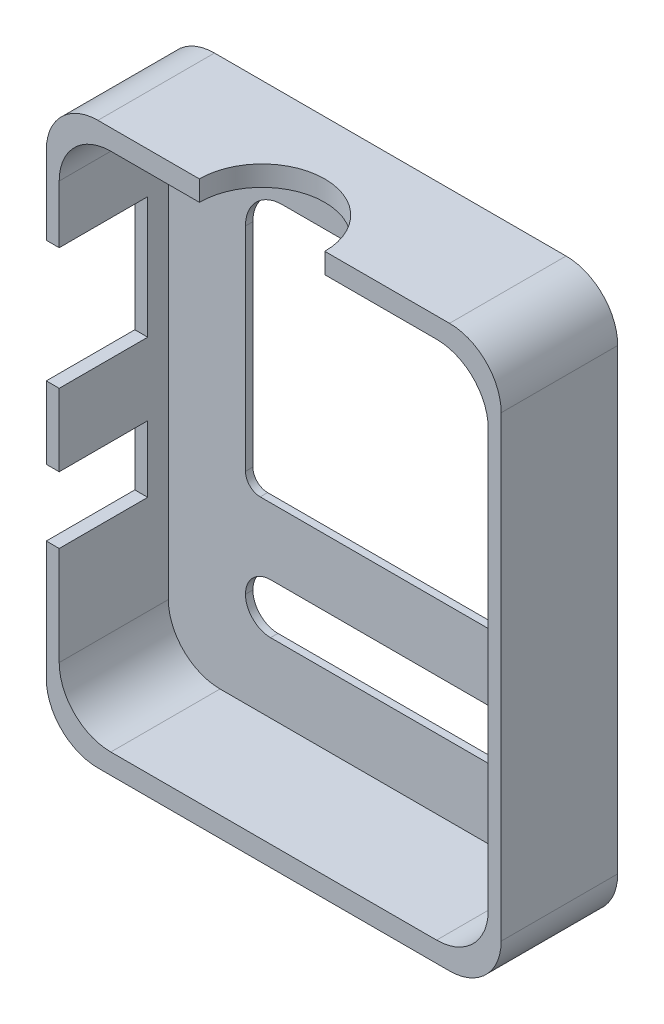
SolidWorks part; units mm, degrees
ref_plane "Front Plane" through (0, 0, 0) normal (0, 0, 1) x (1, 0, 0)
ref_plane "Top Plane" through (0, 0, 0) normal (0, 1, 0) x (1, 0, 0)
ref_plane "Right Plane" through (0, 0, 0) normal (1, 0, 0) x (0, 0, -1)
sketch "Sketch1" plane through (0, 0, 0) normal (0, 0, 1) x (1, 0, 0)
  line L1 (0, 0) -> (61.658, 0)
  line L2 (0, 0) -> (0, 76.028)
  line L3 (0, 76.028) -> (61.658, 76.028)
  line L4 (61.658, 0) -> (61.658, 76.028)
  dimension "D1" = 61.658
  dimension "D2" = 76.2688
extrude "Boss-Extrude1" add sketch "Sketch1" along normal blind 15.8
sketch "Sketch3" plane through (0, 0, 15.8) normal (0, 0, 1) x (1, 0, 0)
  line L0 (0, 76.028) -> (0, 0) construction
  line L1 (1.75, 2.75) -> (59.908, 2.75)
  line L2 (1.75, 2.75) -> (1.75, 73.278)
  line L3 (1.75, 73.278) -> (59.908, 73.278)
  line L4 (59.908, 2.75) -> (59.908, 73.278)
  line L5 (61.658, 76.028) -> (0, 76.028) construction
  dimension "D1" = 70.528
  dimension "D2" = 58.158
  dimension "D3" = 1.75
  dimension "D4" = 2.75
extrude "Cut-Extrude2" cut sketch "Sketch3" against normal blind 14.8
fillet "Fillet1" radius 7 1 edges at (61.658, 76.028, 7.9)
fillet "Fillet2" radius 7 3 edges at (0, 0, 7.9) (61.658, 0, 7.9) (1.75, 73.278, 8.4)
fillet "Fillet3" radius 7 4 edges at (1.75, 2.75, 8.4) (59.908, 73.278, 8.4) (59.908, 2.75, 8.4) (0, 76.028, 7.9)
sketch "Sketch4" plane through (0, 0, 15.8) normal (0, 0, 1) x (1, 0, 0)
  line L0 (0, 69.028) -> (0, 7) construction
  line L1 (0, 58.4447) -> (1.75, 58.4447)
  line L2 (0, 58.4447) -> (0, 41.9447)
  line L3 (0, 41.9447) -> (1.75, 41.9447)
  line L4 (1.75, 58.4447) -> (1.75, 41.9447)
  line L5 (1.75, 66.278) -> (1.75, 9.75) construction
  dimension "D1" = 1.75
  dimension "D2" = 16.5
extrude "Cut-Extrude3_switch" cut sketch "Sketch4" against normal blind 12
sketch "Sketch5" plane through (0, 0, 15.8) normal (0, 0, 1) x (1, 0, 0)
  line L0 (0, 41.9447) -> (0, 7) construction
  line L1 (0, 32.144) -> (1.75, 32.144)
  line L2 (0, 32.144) -> (0, 23.144)
  line L3 (0, 23.144) -> (1.75, 23.144)
  line L4 (1.75, 32.144) -> (1.75, 23.144)
  line L5 (1.75, 66.278) -> (1.75, 9.75) construction
  dimension "D1" = 9
extrude "Cut-Extrude4_usb" cut sketch "Sketch5" against normal blind 12
sketch "Sketch6" plane through (0, 76.028, 0) normal (0, 1, 0) x (1, 0, 0)
  line L0 (54.658, -15.8) -> (7, -15.8) construction
  line L2 (7, 0) -> (7, -15.8) construction
  circle A0 centre (29.25, -15.8) radius 8.5
  point P6 (0, 0)
  point P7 (0, 0)
  dimension "D1" = 22.25
extrude "Cut-Extrude4_sonic" cut sketch "Sketch6" against normal blind 2.75
sketch "Sketch7" plane through (0, 0, 0) normal (0, 0, -1) x (-1, 0, 0)
  line L0 (-61.658, 7) -> (-61.658, 69.028) construction
  line L1 (-49.458, 63.828) -> (-12.2, 63.828)
  line L2 (-49.458, 63.828) -> (-49.458, 28.028)
  line L3 (-49.458, 28.028) -> (-12.2, 28.028)
  line L4 (-12.2, 63.828) -> (-12.2, 28.028)
  line L6 (0, 69.028) -> (0, 7) construction
  line L7 (-54.658, 76.028) -> (-7, 76.028) construction
  point P8 (-30.829, 63.828)
  dimension "D1" = 12.2
  dimension "D2" = 12.2
  dimension "D3" = 12.2
  dimension "D4" = 48
extrude "Cut-Extrude5_LcdMain" cut sketch "Sketch7" against normal blind 1
sketch "Sketch8" plane through (0, 0, 0) normal (0, 0, -1) x (-1, 0, 0)
  line L0 (-61.658, 7) -> (-61.658, 69.028) construction
  line L1 (-49.458, 12.2) -> (-12.2, 12.2)
  line L2 (-49.458, 12.2) -> (-49.458, 19)
  line L3 (-49.458, 19) -> (-12.2, 19)
  line L4 (-12.2, 12.2) -> (-12.2, 19)
  line L5 (0, 69.028) -> (0, 7) construction
  line L6 (-7, 0) -> (-54.658, 0) construction
  dimension "D1" = 12.2
  dimension "D2" = 12.2
  dimension "D3" = 12.2
  dimension "D4" = 19
extrude "Cut-Extrude6_LcdNoti" cut sketch "Sketch8" against normal blind 1
fillet "Fillet4" radius 5 2 edges at (12.2, 63.828, 0.5) (49.458, 63.828, 0.5)
fillet "Fillet5" radius 2 2 edges at (12.2, 28.028, 0.5) (49.458, 28.028, 0.5)
fillet "Fillet6" radius 3.4 4 edges at (12.2, 12.2, 0.5) (12.2, 19, 0.5) (49.458, 19, 0.5) (49.458, 12.2, 0.5)
